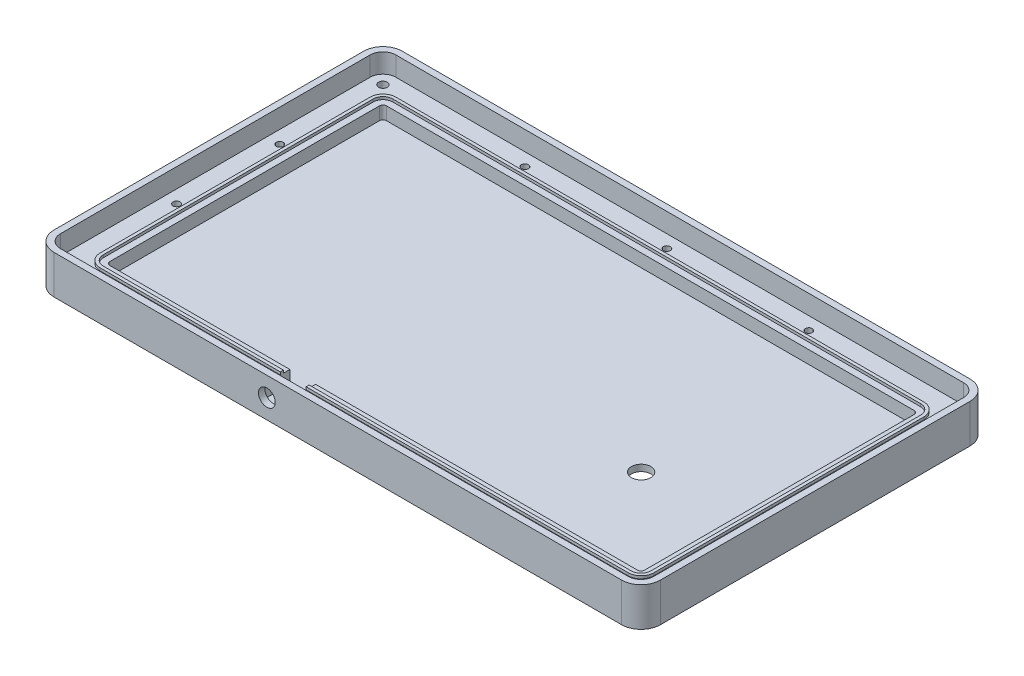
SolidWorks part; units mm, degrees
ref_plane "Front Plane" through (0, 0, 0) normal (0, 0, 1) x (1, 0, 0)
ref_plane "Top Plane" through (0, 0, 0) normal (0, 1, 0) x (1, 0, 0)
ref_plane "Right Plane" through (0, 0, 0) normal (1, 0, 0) x (0, 0, -1)
sketch "Sketch1" plane through (0, 0, 0) normal (0, 1, 0) x (1, 0, 0)
  line L1 (0, 0) -> (298.45, 0)
  line L2 (0, 0) -> (0, 171.45)
  line L3 (0, 171.45) -> (298.45, 171.45)
  line L4 (298.45, 0) -> (298.45, 171.45)
  dimension "D1" = 298.45
  dimension "D2" = 171.45
extrude "Boss-Extrude1" add sketch "Sketch1" along normal blind 19.05
fillet "Fillet1" radius 9.525 4 edges at (298.45, 9.525, 0) (298.45, 9.525, -171.45) (0, 9.525, 0) (0, 9.525, -171.45)
sketch "Sketch3" plane through (0, 19.05, 0) normal (0, 1, 0) x (1, 0, 0)
  line L25 (295.275, 9.525) -> (295.275, 161.925)
  line L26 (9.525, 3.175) -> (288.925, 3.175)
  line L27 (3.175, 161.925) -> (3.175, 9.525)
  line L28 (288.925, 168.275) -> (9.525, 168.275)
  line L29 (295.275, 9.525) -> (295.275, 161.925)
  line L30 (9.525, 3.175) -> (288.925, 3.175)
  line L31 (3.175, 161.925) -> (3.175, 9.525)
  line L32 (288.925, 168.275) -> (9.525, 168.275)
  arc A21 (295.275, 161.925) -> (288.925, 168.275) centre (288.925, 161.925) ccw
  arc A22 (288.925, 3.175) -> (295.275, 9.525) centre (288.925, 9.525) ccw
  arc A23 (3.175, 9.525) -> (9.525, 3.175) centre (9.525, 9.525) ccw
  arc A24 (9.525, 168.275) -> (3.175, 161.925) centre (9.525, 161.925) ccw
  arc A25 (295.275, 161.925) -> (288.925, 168.275) centre (288.925, 161.925) ccw
  arc A26 (288.925, 3.175) -> (295.275, 9.525) centre (288.925, 9.525) ccw
  arc A27 (3.175, 9.525) -> (9.525, 3.175) centre (9.525, 9.525) ccw
  arc A28 (9.525, 168.275) -> (3.175, 161.925) centre (9.525, 161.925) ccw
  dimension "D1" = 3.175
extrude "Cut-Extrude1" cut sketch "Sketch3" against normal blind 9.525
sketch "Sketch5" plane through (0, 9.525, 0) normal (0, 1, 0) x (1, 0, 0)
  line L0 (288.925, 168.275) -> (9.525, 168.275) construction
  line L1 (9.525, 161.925) -> (288.925, 161.925) construction
  line L2 (9.525, 161.925) -> (9.525, 9.525) construction
  line L3 (9.525, 9.525) -> (288.925, 9.525) construction
  line L4 (288.925, 161.925) -> (288.925, 9.525) construction
  line L5 (3.175, 161.925) -> (3.175, 9.525) construction
  line L6 (9.525, 3.175) -> (288.925, 3.175) construction
  line L7 (295.275, 9.525) -> (295.275, 161.925) construction
  circle A0 centre (9.525, 161.925) radius 2.1844
  circle A1 centre (288.925, 161.925) radius 2.1844
  circle A2 centre (9.525, 9.525) radius 2.1844
  circle A3 centre (288.925, 9.525) radius 2.1844
  dimension "D5" = 4.3688
  dimension "D1" = 6.35
  dimension "D2" = 6.35
  dimension "D3" = 6.35
  dimension "D4" = 6.35
extrude "Cut-Extrude2" cut sketch "Sketch5" against normal through all
sketch "Sketch6" plane through (0, 9.525, 0) normal (0, 1, 0) x (1, 0, 0)
  line L1 (9.525, 161.925) -> (288.925, 161.925) construction
  line L2 (9.525, 161.925) -> (9.525, 9.525) construction
  line L3 (9.525, 9.525) -> (288.925, 9.525) construction
  line L4 (288.925, 161.925) -> (288.925, 9.525) construction
  circle A0 centre (9.525, 111.125) radius 1.7272
  circle A1 centre (9.525, 60.325) radius 1.7272
  circle A2 centre (288.925, 111.125) radius 1.7272
  circle A3 centre (79.375, 161.925) radius 1.7272
  circle A4 centre (79.375, 9.525) radius 1.7272
  circle A5 centre (149.225, 9.525) radius 1.7272
  circle A6 centre (219.075, 9.525) radius 1.7272
  circle A7 centre (288.925, 60.325) radius 1.7272
  circle A8 centre (149.225, 161.925) radius 1.7272
  circle A9 centre (219.075, 161.925) radius 1.7272
  dimension "D1" = 3.4544
  dimension "D2" = 50.8
  dimension "D3" = 50.8
  dimension "D4" = 69.85
  dimension "D5" = 69.85
  dimension "D6" = 50.8
  dimension "D7" = 69.85
  dimension "D8" = 69.85
  dimension "D9" = 50.8
extrude "Cut-Extrude3" cut sketch "Sketch6" against normal blind 6.985
sketch "Sketch7" plane through (0, 9.525, 0) normal (0, 1, 0) x (1, 0, 0)
  line L0 (19.304, 156.972) -> (279.146, 156.972)
  line L1 (283.972, 152.146) -> (283.972, 19.304)
  line L2 (19.304, 14.478) -> (279.146, 14.478)
  line L3 (14.478, 152.146) -> (14.478, 19.304)
  line L30 (288.925, 168.275) -> (9.525, 168.275) construction
  line L31 (19.304, 158.496) -> (279.146, 158.496)
  line L32 (12.954, 152.146) -> (12.954, 19.304)
  line L33 (19.304, 12.954) -> (279.146, 12.954)
  line L34 (285.496, 152.146) -> (285.496, 19.304)
  line L35 (3.175, 161.925) -> (3.175, 9.525) construction
  line L36 (9.525, 3.175) -> (288.925, 3.175) construction
  line L37 (295.275, 9.525) -> (295.275, 161.925) construction
  arc A0 (12.954, 19.304) -> (19.304, 12.954) centre (19.304, 19.304) ccw
  arc A1 (279.146, 12.954) -> (285.496, 19.304) centre (279.146, 19.304) ccw
  arc A2 (279.146, 158.496) -> (285.496, 152.146) centre (279.146, 152.146) cw
  arc A3 (19.304, 158.496) -> (12.954, 152.146) centre (19.304, 152.146) ccw
  arc A4 (279.146, 156.972) -> (283.972, 152.146) centre (279.146, 152.146) cw
  arc A5 (279.146, 14.478) -> (283.972, 19.304) centre (279.146, 19.304) ccw
  arc A6 (14.478, 19.304) -> (19.304, 14.478) centre (19.304, 19.304) ccw
  arc A7 (19.304, 156.972) -> (14.478, 152.146) centre (19.304, 152.146) ccw
  dimension "D5" = 6.35
  dimension "D1" = 9.779
  dimension "D2" = 9.779
  dimension "D3" = 9.779
  dimension "D4" = 9.779
  dimension "D6" = 1.524
extrude "Boss-Extrude2" add sketch "Sketch7" along normal blind 1.3208
sketch "Sketch8" plane through (0, 9.525, 0) normal (0, 1, 0) x (1, 0, 0)
  line L24 (280.797, 19.304) -> (280.797, 152.146)
  line L25 (19.304, 17.653) -> (279.146, 17.653)
  line L26 (17.653, 152.146) -> (17.653, 19.304)
  line L27 (279.146, 153.797) -> (19.304, 153.797)
  line L28 (280.797, 19.304) -> (280.797, 152.146)
  line L29 (19.304, 17.653) -> (279.146, 17.653)
  line L30 (17.653, 152.146) -> (17.653, 19.304)
  line L31 (279.146, 153.797) -> (19.304, 153.797)
  arc A20 (280.797, 152.146) -> (279.146, 153.797) centre (279.146, 152.146) ccw
  arc A21 (279.146, 17.653) -> (280.797, 19.304) centre (279.146, 19.304) ccw
  arc A22 (17.653, 19.304) -> (19.304, 17.653) centre (19.304, 19.304) ccw
  arc A23 (19.304, 153.797) -> (17.653, 152.146) centre (19.304, 152.146) ccw
  arc A24 (280.797, 152.146) -> (279.146, 153.797) centre (279.146, 152.146) ccw
  arc A25 (279.146, 17.653) -> (280.797, 19.304) centre (279.146, 19.304) ccw
  arc A26 (17.653, 19.304) -> (19.304, 17.653) centre (19.304, 19.304) ccw
  arc A27 (19.304, 153.797) -> (17.653, 152.146) centre (19.304, 152.146) ccw
  dimension "D1" = 3.175
extrude "Cut-Extrude4" cut sketch "Sketch8" against normal blind 6.35
sketch "Sketch9" plane through (0, 0, 0) normal (0, 0, 1) x (1, 0, 0)
  line L0 (9.525, 19.05) -> (288.925, 19.05) construction
  line L1 (0, 0) -> (0, 19.05) construction
  circle A0 centre (114.3, 9.525) radius 4.1275
  dimension "D3" = 8.255
  dimension "D1" = 9.525
  dimension "D2" = 114.3
extrude "Cut-Extrude5" cut sketch "Sketch9" against normal blind 25.4
sketch "Sketch11" plane through (0, 0, -17.653) normal (0, 0, -1) x (-1, 0, 0)
  circle A0 centre (-114.3, 9.525) radius 6.35
  dimension "D1" = 12.7
extrude "Cut-Extrude6" cut sketch "Sketch11" against normal up to surface (14.478 mm away) up to face at (137.5833, 13.3879, -3.175)
sketch "Sketch12" plane through (0, 10.8458, 0) normal (0, 1, 0) x (1, 0, 0)
  line L1 (107.95, 3.175) -> (120.65, 3.175)
  line L2 (107.95, 3.175) -> (107.95, 17.653)
  line L3 (107.95, 17.653) -> (120.65, 17.653)
  line L4 (120.65, 3.175) -> (120.65, 17.653)
extrude "Cut-Extrude7" cut sketch "Sketch12" against normal up to surface (7.6708 mm away) up to face at (145.3444, 3.175, -78.1614)
ref_plane "Plane1" through (295.275, 0, -314.325) normal (0, 0, 1) x (1, 0, 0)
sketch "Sketch15" plane through (0, 3.175, 0) normal (0, 1, 0) x (1, 0, 0)
  line L0 (298.45, 9.525) -> (298.45, 161.925) construction
  line L1 (9.525, 0) -> (288.925, 0) construction
  circle A0 centre (231.8004, 66.7004) radius 4.7625
  dimension "D1" = 9.525
  dimension "D2" = 66.6496
  dimension "D3" = 66.7004
extrude "Cut-Extrude8" cut sketch "Sketch15" against normal through all
